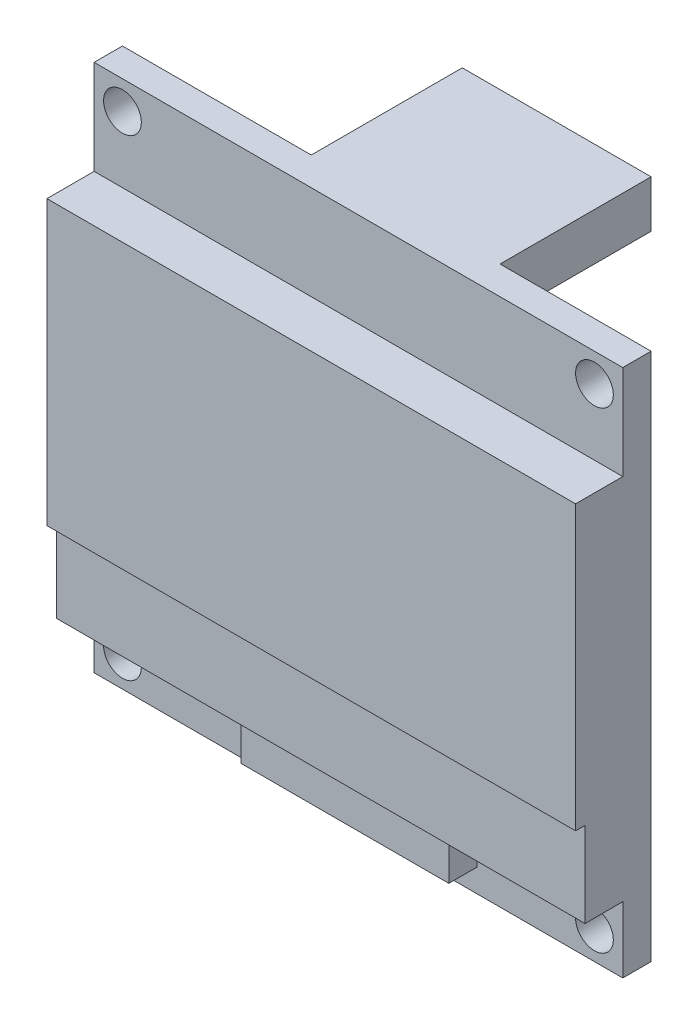
SolidWorks part; units mm, degrees
ref_plane "Спереди" through (0, 0, 0) normal (0, 0, 1) x (1, 0, 0)
ref_plane "Сверху" through (0, 0, 0) normal (0, 1, 0) x (1, 0, 0)
ref_plane "Справа" through (0, 0, 0) normal (1, 0, 0) x (0, 0, -1)
sketch "Эскиз1" plane through (0, 0, 0) normal (0, 0, 1) x (1, 0, 0)
  line L1 (0, 0) -> (28, 0)
  line L2 (0, 0) -> (0, 28)
  line L3 (0, 28) -> (28, 28)
  line L4 (28, 0) -> (28, 28)
extrude "Бобышка-Вытянуть3" add sketch "Эскиз1" along normal blind 1.5
sketch "Эскиз3" plane through (0, 0, 1.5) normal (0, 0, 1) x (1, 0, 0)
  line L0 (0, 28) -> (0, 0) construction
  line L1 (0, 23) -> (28, 23)
  line L2 (0, 23) -> (0, 3.5)
  line L3 (0, 3.5) -> (28, 3.5)
  line L4 (28, 23) -> (28, 3.5)
  line L5 (28, 0) -> (28, 28) construction
  point P8 (0, 0)
  point P10 (0, 0)
  dimension "D1" = 19.5
  dimension "D2" = 5
extrude "Бобышка-Вытянуть4" add sketch "Эскиз3" along normal blind 2
sketch "Эскиз5" plane through (0, 0, 3.5) normal (0, 0, 1) x (1, 0, 0)
  line L0 (28, 3.5) -> (28, 23) construction
  line L1 (0, 23) -> (28, 23)
  line L2 (0, 23) -> (0, 8)
  line L3 (0, 8) -> (28, 8)
  line L4 (28, 23) -> (28, 8)
extrude "Бобышка-Вытянуть5" add sketch "Эскиз5" along normal blind 0.5
sketch "Эскиз6" plane through (0, 0, 1.5) normal (0, 0, 1) x (1, 0, 0)
  line L0 (0, 3.5) -> (28, 3.5) construction
  line L1 (9.2875, 3.5) -> (20.2875, 3.5)
  line L2 (9.2875, 3.5) -> (9.2875, 1.2336)
  line L3 (9.2875, 1.2336) -> (20.2875, 1.2336)
  line L4 (20.2875, 3.5) -> (20.2875, 1.2336)
  line M5 (28, 3.5) -> (0, 3.5)
extrude "Бобышка-Вытянуть6" add sketch "Эскиз6" along normal blind 1.5 contours L4 L2 L3 M5 | L2 L1 L4 L3 region at (14.7875, 2.3668, 1.5)
sketch "Эскиз7" plane through (0, 0, 1.5) normal (0, 0, 1) x (1, 0, 0)
  line L0 (0, 3.5) -> (0, 0) construction
  line L1 (0, 0) -> (28, 0) construction
  line L2 (28, 28) -> (0, 28) construction
  line L3 (0, 28) -> (0, 23) construction
  line L4 (28, 0) -> (28, 3.5) construction
  line L5 (28, 23) -> (28, 28) construction
  circle A0 centre (1.5, 1.5) radius 1
  circle A1 centre (1.5, 26.5) radius 1
  circle A2 centre (26.5, 26.5) radius 1
  circle A3 centre (26.5, 1.5) radius 1
  point P8 (0, 0)
  point P21 (0, 0)
  dimension "D1" = 1.5
  dimension "D3" = 1.5
  dimension "D5" = 1.5
  dimension "D2" = 1.5
  dimension "D4" = 1.5
  dimension "D6" = 1.5
  dimension "D7" = 1.5
  dimension "D8" = 1.5
extrude "Вырез-Вытянуть4" cut sketch "Эскиз7" against normal blind 1.5
sketch "Эскиз10" plane through (0, 0, 0) normal (0, 0, -1) x (-1, 0, 0)
  line L0 (-28, 28) -> (0, 28) construction
  line L1 (-20, 28) -> (-10, 28)
  line L2 (-20, 28) -> (-20, 25.5)
  line L3 (-20, 25.5) -> (-10, 25.5)
  line L4 (-10, 28) -> (-10, 25.5)
  dimension "D1" = 10
  dimension "D2" = 2.5
  dimension "D3" = 8
extrude "Бобышка-Вытянуть8" add sketch "Эскиз10" along normal blind 8
